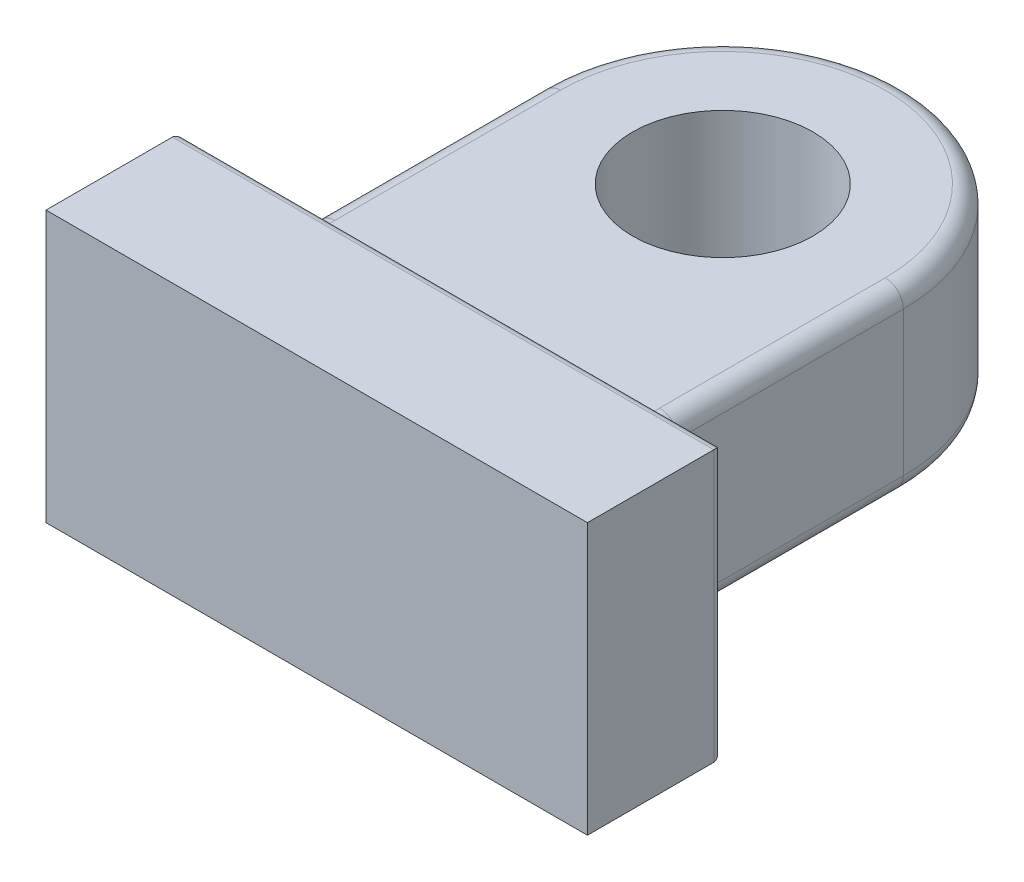
SolidWorks part; units mm, degrees
ref_plane "Front Plane" through (0, 0, 0) normal (0, 0, 1) x (1, 0, 0)
ref_plane "Top Plane" through (0, 0, 0) normal (0, 1, 0) x (1, 0, 0)
ref_plane "Right Plane" through (0, 0, 0) normal (1, 0, 0) x (0, 0, -1)
sketch "Sketch1" plane through (0, 0, 0) normal (0, 0, 1) x (1, 0, 0)
  line L1 (-30, 15) -> (30, 15)
  line L2 (-30, 15) -> (-30, -15)
  line L3 (-30, -15) -> (30, -15)
  line L4 (30, 15) -> (30, -15)
  line L5 (-30, 15) -> (30, -15) construction
  line L6 (-30, -15) -> (30, 15) construction
  point P0 (0, 0)
  dimension "D1" = 60
  dimension "D2" = 30
extrude "Boss-Extrude1" add sketch "Sketch1" along normal blind 15
sketch "Sketch2" plane through (0, 0, 0) normal (0, 1, 0) x (1, 0, 0)
  line L0 (0, 0) -> (0, 30) construction
  line L1 (20, 30) -> (20, 0)
  line L2 (30, 0) -> (-30, 0) construction
  line L3 (-20, 30) -> (-20, 0)
  line L4 (-20, 0) -> (20, 0)
  arc A0 (20, 30) -> (-20, 30) centre (0, 30) ccw
  circle A1 centre (0, 30) radius 10
  dimension "D1" = 30
  dimension "D2" = 20
  dimension "D3" = 20
extrude "Boss-Extrude2" add sketch "Sketch2" along normal mid plane 20
fillet "Fillet1" radius 5 2 edges at (-20, 0, 0) (20, 0, 0)
fillet "Fillet2" radius 2 10 edges at (21.4645, -10, -1.4645) (20, -10, -17.5) (-21.4645, -10, -1.4645) (-20, -10, -17.5) (-21.4645, 10, -1.4645) (-20, 10, -17.5) (0, 10, -50) (0, -10, -50) (21.4645, 10, -1.4645) (20, 10, -17.5)
fillet "Fillet3" radius 1 10 edges at (0, 15, 0) (-30, 0, 0) (0, -15, 0) (30, 0, 0) (21.6773, 9.734, 0) (21.6773, -9.734, 0) (0, -10, 0) (-21.6773, -9.734, 0) (-21.6773, 9.734, 0) (0, 10, 0)
